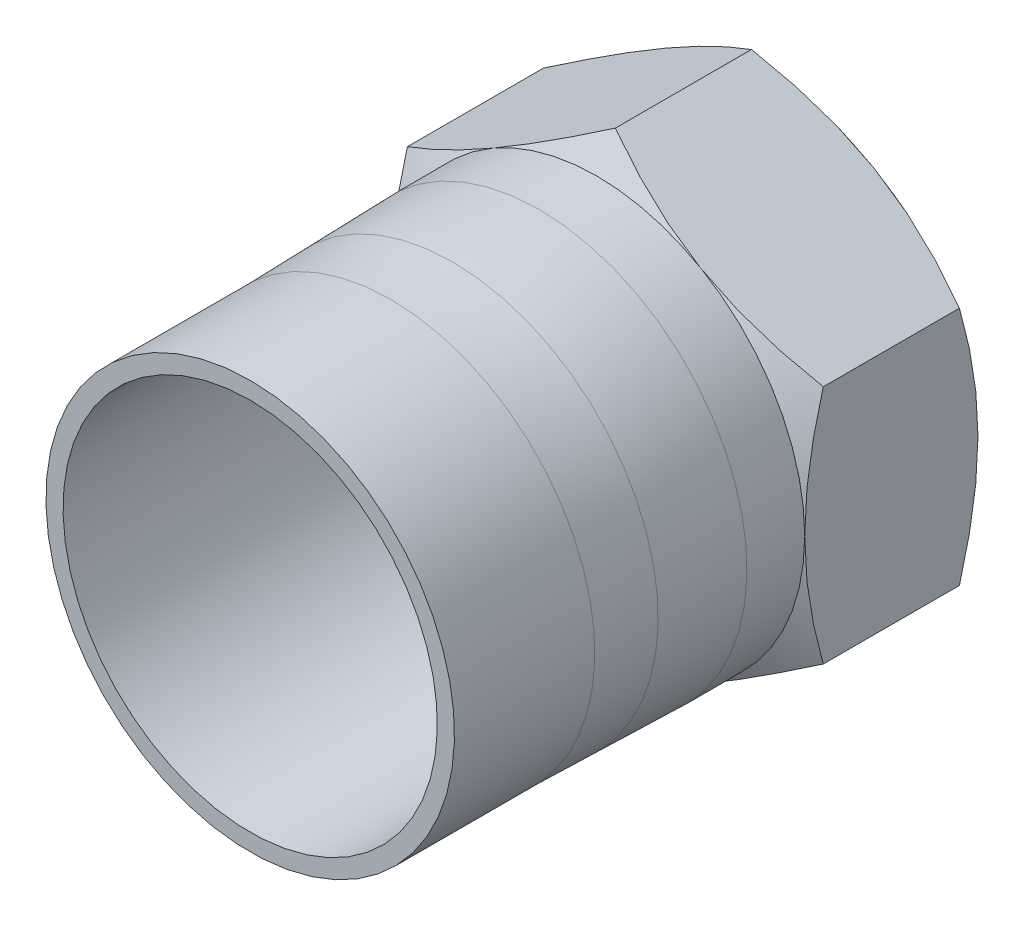
SolidWorks part; units mm, degrees
material "Copper"
ref_plane "Front Plane" through (0, 0, 0) normal (0, 0, 1) x (1, 0, 0)
ref_plane "Top Plane" through (0, 0, 0) normal (0, 1, 0) x (1, 0, 0)
ref_plane "Right Plane" through (0, 0, 0) normal (1, 0, 0) x (0, 0, -1)
sketch "Sketch1" plane through (0, 0, 0) normal (1, 0, 0) x (0, 0, -1)
  line L0 (0, 0) -> (0, 15.875) construction
  line L1 (0, 0) -> (-23.0188, 0) construction
  line L2 (0, 0) -> (16.6687, 0) construction
  line L3 (5.5801, 0) -> (5.5801, 12.9898) construction
  line L4 (-23.0188, 14.2875) -> (-23.0188, -14.2875) construction
  line L5 (16.6688, 10.4648) -> (16.6688, -10.4648) construction
  line L6 (16.6688, 10.4648) -> (18.483, 10.4648) construction
  line L7 (-23.0188, 14.2875) -> (0, 14.2875) construction
  line L8 (0, 14.2875) -> (1.9182, 11.43) construction
  line L9 (1.9182, 11.43) -> (3.8365, 11.43) construction
  line L10 (3.8365, 11.43) -> (5.5801, 12.9898) construction
  line L11 (1.9182, 11.43) -> (0, 11.43) construction
  line L12 (16.6687, 11.9343) -> (15.1993, 10.4648) construction
  line L14 (0, 14.2875) -> (0, 11.43) construction
  line L15 (0, 15.875) -> (-26.8288, 15.875) construction
  line L16 (5.5801, 12.9898) -> (16.6687, 13.335) construction
  point P0 (-23.0188, 15.5956)
  point P17 (16.6687, 15.875)
  point P26 (16.6688, 10.4648)
  point P27 (16.6687, 13.335)
  point P29 (16.6687, -13.335)
  dimension "Hex" = 31.75
  dimension "Socket Depth" = 23.0188
  dimension "For Tube OD" = 28.575
  dimension "Pipe ID" = 20.9296
  dimension "NPT Thread Engagement" = 11.0886
  dimension "Pitch" = 1.8143
  dimension "Length" = 39.6875
  dimension "Tube End OD" = 31.1912
  dimension "D1" = 1.9182
  dimension "D2" = 45
  dimension "To Hex Face" = 3.81
  dimension "D7" = 2.0782
  dimension "Pipe Size" = 26.67
  dimension "D4" = 1.783
  dimension "D3" = 22.86
sketch "Sketch2" plane through (0, 0, 0) normal (0, 0, 1) x (1, 0, 0)
  line L1 (0, 18.3309) -> (-15.875, 9.1654)
  line L2 (-15.875, 9.1654) -> (-15.875, -9.1654)
  line L3 (-15.875, -9.1654) -> (0, -18.3309)
  line L4 (0, -18.3309) -> (15.875, -9.1654)
  line L5 (15.875, -9.1654) -> (15.875, 9.1654)
  line L6 (15.875, 9.1654) -> (0, 18.3309)
  circle A0 centre (0, 0) radius 15.875 construction
  dimension "D1" = 31.75
extrude "Boss-Extrude1" add sketch "Sketch2" along normal up to vertex (23.0188 mm away) and the other way up to vertex (16.6687 mm away) up to point (0, 0, 23.0188) other way up to point (0, 0, -16.6687)
sketch "Sketch22" plane through (0, 0, -16.6687) normal (0, 0, -1) x (-1, 0, 0)
  circle A0 centre (0, 0) radius 15.875 construction
  dimension "D1" = 31.75
sketch "Sketch24" plane through (0, 0, 0) normal (1, 0, 0) x (0, 0, -1)
  line L0 (3.4396, 15.875) -> (-0.9701, 15.875) construction
  line L1 (-23.0188, 9.1654) -> (-23.0188, 18.3309) construction
  line L2 (0, 15.875) -> (-26.8288, 15.875) construction
  line L3 (16.6687, -15.875) -> (16.6687, 15.875) construction
  line L4 (-23.0188, 14.2875) -> (0, 14.2875) construction
  line L5 (-23.0188, 14.2875) -> (0, 14.2875) construction
  line L6 (-23.0188, 15.5956) -> (-23.0188, 18.3309)
  line L7 (-12.3031, 15.5956) -> (-23.0188, 15.5956)
  line L8 (-23.0188, 18.3309) -> (3.4396, 18.3309)
  line L9 (3.4396, 18.3309) -> (3.4396, 15.875)
  line L10 (3.4396, 15.875) -> (-0.9701, 15.875)
  line L12 (-23.0188, 18.3309) -> (16.6687, 18.3309) construction
  arc A0 (-0.9701, 15.875) -> (-7.5847, 15.7119) centre (-0.9701, -118.3565) ccw
  arc A1 (-7.5847, 15.7119) -> (-12.3031, 15.5956) centre (-12.3031, 111.3474) cw
  dimension "D1" = 13.2292
  dimension "D2" = 4.4097
  dimension "D3" = 6.6146
  dimension "D5" = 10.7156
ref_plane "Plane1" through (0, 0, -3.4396) normal (0, 0, 1) x (1, 0, 0)
sketch "Sketch5" plane through (0, 0, 0) normal (1, 0, 0) x (0, 0, -1)
  line L0 (-23.0188, 14.2875) -> (0, 14.2875) construction
  line L1 (0, 14.2875) -> (1.9182, 11.43) construction
  line L3 (3.8365, 11.43) -> (5.5801, 12.9898) construction
  line L4 (-23.0188, 14.2875) -> (0, 14.2875)
  line L5 (0, 14.2875) -> (1.9182, 11.43)
  line L6 (1.9182, 11.43) -> (3.8365, 11.43)
  line L7 (3.8365, 11.43) -> (5.5801, 12.9898)
  line L8 (5.5801, 12.9898) -> (16.6688, 13.335)
  line L9 (1.9182, 11.43) -> (3.8365, 11.43) construction
  line L11 (16.6688, 13.335) -> (16.6688, 0)
  line L12 (16.6688, 10.4648) -> (16.6688, -10.4648) construction
  line L13 (16.6688, 0) -> (-23.0188, 0)
  line L14 (-23.0188, 0) -> (-23.0188, 14.2875)
  line L16 (5.5801, 12.9898) -> (16.6687, 13.335) construction
revolve "Cut-Revolve1" cut sketch "Sketch5" angle 360 about L13
sketch "Sketch10" [suppressed] plane through (0, 0, -16.6687) normal (0, 0, -1) x (-1, 0, 0)
  circle A1 centre (0, 0) radius 13.335
revolve "Cut-Revolve2" cut sketch "Sketch24" angle 360 about L1
sketch "Sketch8" plane through (0, 0, -16.6687) normal (0, 0, 1) x (1, 0, 0)
  circle A1 centre (0, 0) radius 15.875
  dimension "D1" = 31.75
extrude "Cut-Extrude7" cut sketch "Sketch8" along normal blind 2032 draft 60 flip side to cut
sketch "Sketch20" plane through (0, 0, -3.4396) normal (0, 0, -1) x (-1, 0, 0)
  circle A0 centre (0, 0) radius 15.875
  dimension "D1" = 31.75
extrude "Cut-Extrude9" cut sketch "Sketch20" along normal blind 2.54 draft 60 flip side to cut
chamfer "Chamfer1" distance 1.0668 angle 45 1 edges at (0, 13.335, -16.6688) first distance on face at (0, 0, -16.6687)
curve "Helix/Spiral1" [suppressed]
sketch "Sketch9" [suppressed] plane through (0, 0, 0) normal (1, 0, 0) x (0, 0, -1)
  line L0 (18.3696, 13.5314) -> (16.5554, 13.5314) construction
  line L1 (16.5554, 13.5314) -> (17.4625, 11.9602) construction
  line L2 (17.4625, 11.9602) -> (18.3696, 13.5314) construction
  line L3 (18.2562, 13.335) -> (16.6687, 13.335) construction
  line L4 (17.4625, 13.5314) -> (17.4625, 13.335) construction
  line L5 (18.3129, 13.4332) -> (16.6121, 13.4332) construction
  line L6 (17.5759, 12.1566) -> (17.3491, 12.1566) construction
  line L7 (17.4625, 12.1566) -> (17.4625, 11.9602) construction
  line L8 (16.6121, 13.4332) -> (18.3129, 13.4332)
  line L9 (18.3129, 13.4332) -> (17.5759, 12.1566)
  line L10 (17.5759, 12.1566) -> (17.3491, 12.1566)
  line L11 (17.3491, 12.1566) -> (16.6121, 13.4332)
  point P11 (17.4625, 13.4332)
  dimension "D1" = 1.8143
  dimension "D2" = 0.2268
sweep "Sweep1" [suppressed] add profiles "Sketch9" path "Helix/Spiral1"
sketch "Sketch18" [suppressed] plane through (0, 0, -16.6687) normal (0, 0, -1) x (-1, 0, 0)
  circle A0 centre (0, 0) radius 14.4018 construction
  circle A1 centre (0, 0) radius 14.4018
extrude "Cut-Extrude8" [suppressed] cut sketch "Sketch18" along normal blind 2.54 draft 80 and the other way through all draft 45 draft outward yes
equation "\"D1@Sketch1\" = \"Socket Depth@Sketch1\" / 12"
equation "\"D1@Sketch2\" = \"Hex@Sketch1\""
equation "\"D7@Sketch1\" = \"D3@Sketch1\" / 11"
equation "\"D4@Helix/Spiral1\" = \"Pitch@Sketch1\""
equation "\"D3@Helix/Spiral1\" = \"NPT Thread Engagement@Sketch1\" +  ( \"Pitch@Sketch1\" * 1 ) "
equation "\"D1@Sketch20\" = \"Hex@Sketch1\""
equation "\"D1@Sketch8\" = \"Hex@Sketch1\""
equation "\"D1@Sketch22\" = \"Hex@Sketch1\""
equation "\"D1@Sketch24\"=\"Length@Sketch1\" / 3"
equation "\"D2@Sketch24\" = \"D1@Sketch24\"/3"
equation "\"D3@Sketch24\" = \"D2@Sketch24\"*1.5"
equation "\"D1@Chamfer1\" = \"Pipe Size@Sketch1\" * .04"
equation "\"D5@Sketch24\" = \"Length@Sketch1\" * .27"
equation "\"D1@Sketch9\" = \"Pitch@Sketch1\""
equation "\"D2@Sketch9\"=\"D1@Sketch9\"/ 1/8"
equation "\"D3@Sketch1\" = \"For Tube OD@Sketch1\" * .8"
